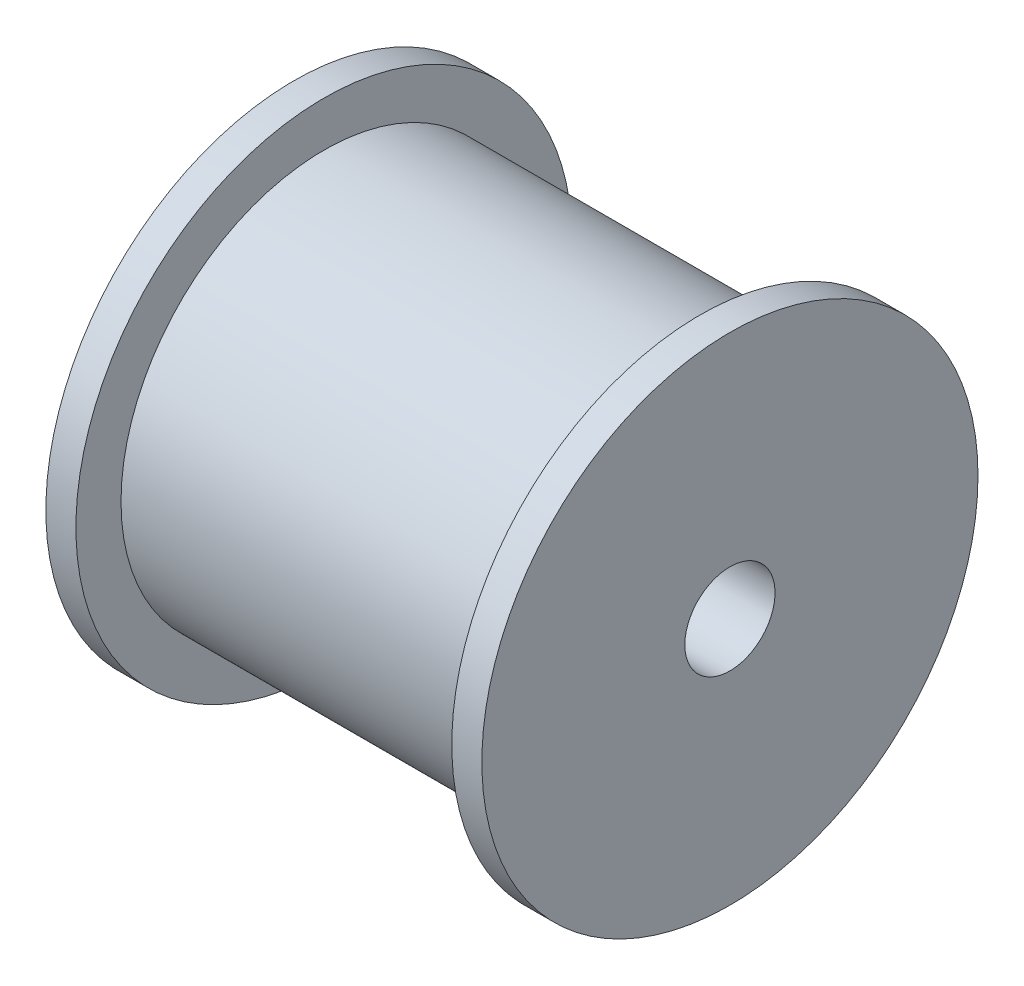
SolidWorks part; units mm, degrees
material "Plain Carbon Steel"
ref_plane "Front Plane" through (0, 0, 0) normal (0, 0, 1) x (1, 0, 0)
ref_plane "Top Plane" through (0, 0, 0) normal (0, 1, 0) x (1, 0, 0)
ref_plane "Right Plane" through (0, 0, 0) normal (1, 0, 0) x (0, 0, -1)
sketch "Sketch1" plane through (0, 0, 0) normal (1, 0, 0) x (0, 0, -1)
  circle A0 centre (0, 0) radius 135
  dimension "D2" = 270
extrude "Boss-Extrude1" add sketch "Sketch1" along normal blind 250
sketch "Sketch2" plane through (0, 0, 0) normal (1, 0, 0) x (0, 0, -1)
  circle A0 centre (0, 0) radius 135 construction
  circle A1 centre (0, 0) radius 135 construction
  circle A2 centre (0, 0) radius 165
  dimension "D1" = 30
extrude "Boss-Extrude2" add sketch "Sketch2" against normal blind 20
ref_plane "Plane1" through (125, 0, 0) normal (1, 0, 0) x (0, 0, -1)
mirror "Mirror1" about plane through (125, 0, 0) normal (1, 0, 0) of "Boss-Extrude2"
sketch "Sketch3" plane through (-20, 0, 0) normal (-1, 0, 0) x (0, 0, 1)
  circle A0 centre (0, 0) radius 30
  dimension "D1" = 60
extrude "Cut-Extrude1" cut sketch "Sketch3" against normal through all
